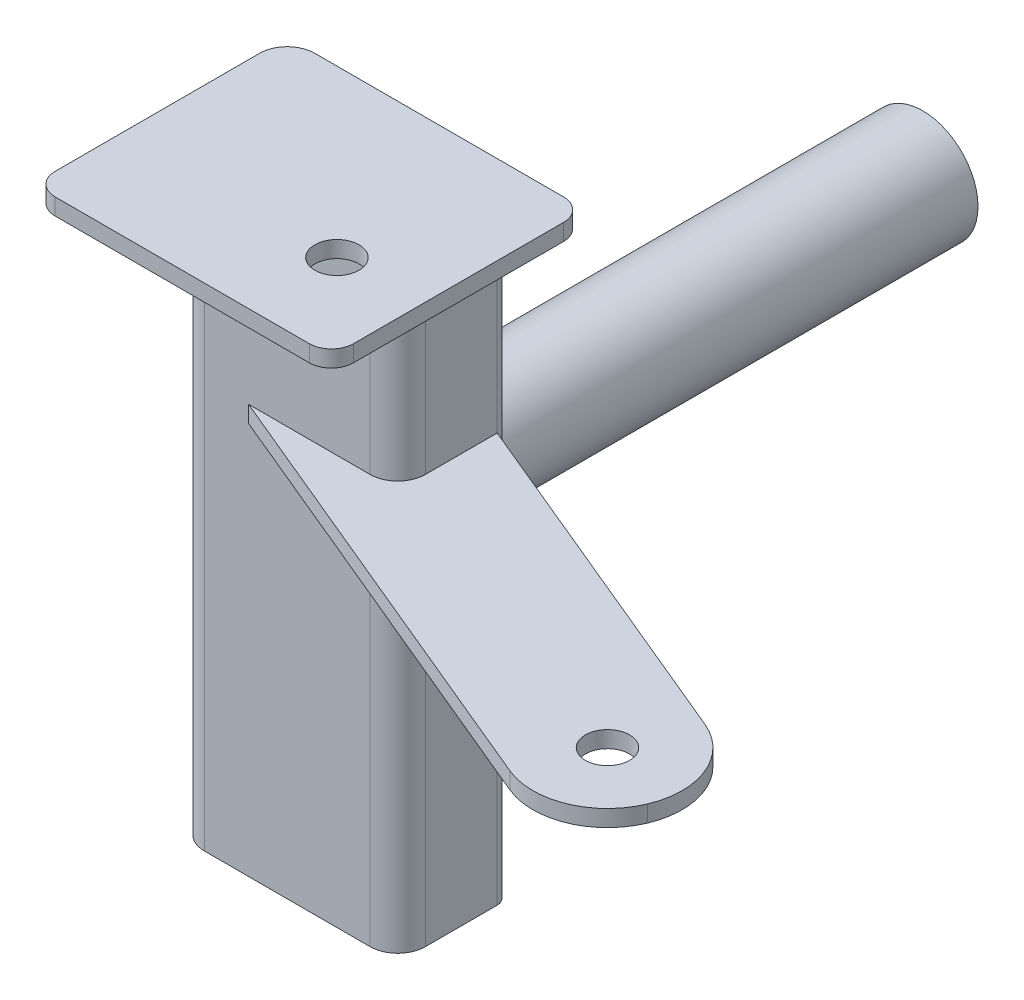
SolidWorks part; units mm, degrees
ref_plane "Front Plane" through (0, 0, 0) normal (0, 0, 1) x (1, 0, 0)
ref_plane "Top Plane" through (0, 0, 0) normal (0, 1, 0) x (1, 0, 0)
ref_plane "Right Plane" through (0, 0, 0) normal (1, 0, 0) x (0, 0, -1)
sketch "Sketch1" plane through (0, 0, 0) normal (0, 1, 0) x (1, 0, 0)
  line L1 (0, 0) -> (40, 0)
  line L2 (0, 0) -> (0, 20)
  line L3 (0, 20) -> (40, 20)
  line L4 (40, 0) -> (40, 20)
  line L5 (0, 0) -> (40, 20) construction
  line L6 (0, 20) -> (40, 0) construction
  point P4 (20, 10)
  dimension "D1" = 40
  dimension "D2" = 20
extrude "Boss-Extrude1" add sketch "Sketch1" along normal blind 115
sketch "Sketch2" plane through (0, 115, 0) normal (0, 1, 0) x (1, 0, 0)
  line L1 (0, 20) -> (54, 20)
  line L2 (0, 20) -> (0, -26)
  line L3 (0, -26) -> (54, -26)
  line L4 (54, 20) -> (54, -26)
  line L5 (0, 20) -> (54, -26) construction
  line L6 (0, -26) -> (54, 20) construction
  line L7 (40, 0) -> (0, 0)
  line L8 (40, 0) -> (40, 20)
  line L9 (40, 20) -> (0, 20)
  line L10 (0, 0) -> (0, 20)
  line L11 (40, 0) -> (0, 20) construction
  line L12 (40, 20) -> (0, 0) construction
  circle A0 centre (39, -10) radius 4
  point P4 (27, -3)
  point P13 (20, 10)
  line M6 (0, 0) -> (40, 0)
  line M7 (40, 0) -> (40, 20)
  dimension "D1" = 8
  dimension "D4" = 16
  dimension "D5" = 15
  dimension "D2" = 46
  dimension "D3" = 54
extrude "Boss-Extrude2" add sketch "Sketch2" against normal blind 3 contours L4 L1 L2 L3 A0 M7 M6 region at (30.0585, 115, 9.1504)
sketch "Sketch3" plane through (0, 0, -20) normal (0, 0, 1) x (1, 0, 0)
  line L0 (40, 112) -> (0, 0) construction
  line L1 (0, 112) -> (40, 0) construction
  circle A0 centre (20, 56) radius 10
  circle A1 centre (20, 56) radius 4
  dimension "D1" = 20
  dimension "D2" = 8
extrude "Boss-Extrude3" add sketch "Sketch3" against normal blind 95
sketch "Sketch4" plane through (0, 0, 0) normal (0, -1, 0) x (1, 0, 0)
  line L0 (40, 0) -> (0, -20) construction
  line L1 (0, -20) -> (0, 0) construction
  line L2 (0, 0) -> (40, -20) construction
  circle A0 centre (20, -10) radius 4
  dimension "D1" = 8
extrude "Cut-Extrude1" cut sketch "Sketch4" against normal blind 18
ref_plane "Plane1" through (0, 74, 0) normal (0, -1, 0) x (-1, 0, 0)
sketch "Sketch5" plane through (0, 74, 0) normal (0, -1, 0) x (-1, 0, 0)
  line L0 (-13, 0) -> (-106.5502, -38.9792)
  line L1 (-106.5502, -38.9792) -> (-116.9348, -14.0562)
  line L2 (-116.9348, -14.0562) -> (-40, 18)
  line L4 (0, 0) -> (0, 20)
  line L5 (0, 20) -> (-40, 20)
  line L6 (-40, 20) -> (-40, 0)
  line L7 (-40, 0) -> (0, 0)
  line L10 (-40, 18) -> (-40, 0)
  line L11 (-40, 0) -> (-13, 0)
  line L15 (0, 20) -> (0, 0) construction
  line L16 (-116.9348, -14.0562) -> (-106.5502, -38.9792)
  line L17 (-116.9348, -14.0562) -> (-92.0117, -3.6715)
  line L19 (-106.5502, -38.9792) -> (-81.6271, -28.5946)
  line L20 (-92.0117, -3.6715) -> (-81.6271, -28.5946) construction
  line L21 (-116.9348, -14.0562) -> (-81.6271, -28.5946) construction
  line L22 (-106.5502, -38.9792) -> (-92.0117, -3.6715) construction
  line L23 (-40, 0) -> (-99.2809, -21.3254) construction
  line L24 (-40, 0) -> (-40, 20) construction
  line L25 (-40, 20) -> (0, 20) construction
  circle A1 centre (-99.2809, -21.3254) radius 4
  point P12 (-99.2809, -21.3254)
  dimension "D3" = 8
  dimension "D2" = 13
  dimension "D4" = 27
  dimension "D5" = 63
  dimension "D6" = 2
  dimension "D1" = 0
extrude "Boss-Extrude4" add sketch "Sketch5" along normal blind 3 contours L11 L10 L2 L1 L0 A1 region at (72.2986, 74, 10.4969)
fillet "Fillet3" radius 5 1 edges at (0, 57.5, -20)
fillet "Fillet4" radius 5 1 edges at (40, 93, 0)
fillet "Fillet5" radius 5 1 edges at (0, 56, 0)
fillet "Fillet6" radius 5 1 edges at (40, 35.5, 0)
fillet "Fillet1" radius 13.5 2 edges at (106.5502, 72.5, 38.9792) (116.9348, 72.5, 14.0562)
fillet "Fillet9" radius 2 1 edges at (40, 56, -20)
fillet "Fillet10" radius 4 3 edges at (54, 113.5, -20) (54, 113.5, 26) (0, 113.5, 26)
sketch "Sketch6" plane through (0, 0, 0) normal (-1, 0, 0) x (0, 0, 1)
  line L0 (-10, 91.5) -> (-10, 15) construction
  line L2 (-10, 15) -> (-10, 0) construction
  line L3 (-15, 0) -> (-5, 0) construction
  circle A0 centre (-10, 91.5) radius 3.5
  circle A1 centre (-10, 15) radius 3.5
  dimension "D1" = 7
  dimension "D2" = 7
  dimension "D3" = 15
  dimension "D4" = 76.5
extrude "Cut-Extrude2" cut sketch "Sketch6" against normal blind 12
